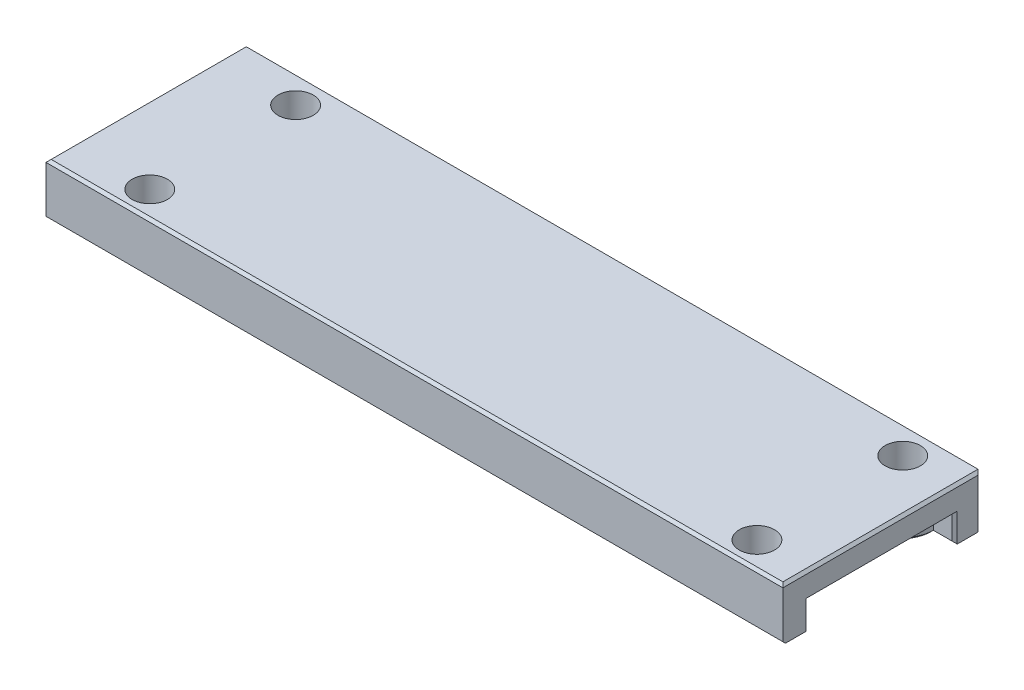
SolidWorks part; units mm, degrees
material "1060 Alloy"
ref_plane "Front Plane" through (0, 0, 0) normal (0, 0, 1) x (1, 0, 0)
ref_plane "Top Plane" through (0, 0, 0) normal (0, 1, 0) x (1, 0, 0)
ref_plane "Right Plane" through (0, 0, 0) normal (1, 0, 0) x (0, 0, -1)
sketch "Sketch1" plane through (0, 0, 0) normal (0, 1, 0) x (1, 0, 0)
  line L1 (-71, -19.05) -> (71, -19.05)
  line L2 (-71, -19.05) -> (-71, 19.05)
  line L3 (-71, 19.05) -> (71, 19.05)
  line L4 (71, -19.05) -> (71, 19.05)
  line L5 (-71, -19.05) -> (71, 19.05) construction
  line L6 (-71, 19.05) -> (71, -19.05) construction
  point P0 (0, 0)
  dimension "D1" = 142
  dimension "D2" = 38.1
extrude "Boss-Extrude1" add sketch "Sketch1" along normal mid plane 10
sketch "Sketch2" plane through (0, 0, 0) normal (1, 0, 0) x (0, 0, -1)
  line L0 (-14.05, 0) -> (14.05, 0)
  line L1 (14.05, 0) -> (14.05, -5)
  line L2 (-19.05, -5) -> (19.05, -5) construction
  line L3 (14.05, -5) -> (-14.05, -5)
  line L4 (-14.05, -5) -> (-14.05, 0)
  line L5 (-19.05, 5) -> (-19.05, -5) construction
  dimension "D1" = 5
extrude "Cut-Extrude1" cut sketch "Sketch2" against normal through all both and the other way through all
hole_wizard "Tap Drill for M8x1.25 Tap1" positions "Sketch4" profile "Sketch3" hole size "M8x1.25" standard "ANSI Metric"
sketch "Sketch4" plane through (0, 5, 0) normal (0, 1, 0) x (1, 0, 0)
  line L0 (71, 19.05) -> (-71, 19.05) construction
  line L2 (-71, 19.05) -> (-71, -19.05) construction
  line L3 (-71, -19.05) -> (71, -19.05) construction
  line L4 (71, -19.05) -> (71, 19.05) construction
  point P0 (-56, 14.05)
  point P2 (61, 14.05)
  point P4 (61, -14.05)
  point P6 (-56, -14.05)
  dimension "D1" = 5
  dimension "D2" = 15
  dimension "D3" = 15
  dimension "D4" = 5
  dimension "D5" = 10
  dimension "D6" = 10
  dimension "D7" = 5
  dimension "D8" = 5
sketch "Sketch3" plane through (-56, 5, -14.05) normal (1, 0, 0) x (0, 0, 1)
  line L0 (0, 0) -> (0, 14.0429)
  line L1 (0, 14.0429) -> (3.4, 12)
  line L2 (3.4, 12) -> (3.4, 0)
  line L5 (3.4, 0) -> (0, 0)
  line L10 (0, 14.0429) -> (-3.4, 12) construction
  line L11 (0, -6.35) -> (0, 107.95) construction
  dimension "Hole Dia." = 6.8
  dimension "Hole Depth" = 12
  dimension "Drill Angle" = 118
cosmetic thread "Cosmetic Thread1" parameters "D2"=8
cosmetic thread "Cosmetic Thread2" parameters "D2"=8
cosmetic thread "Cosmetic Thread3" parameters "D2"=8
cosmetic thread "Cosmetic Thread4" parameters "D2"=8
sketch "Sketch5" plane through (0, 0, 0) normal (0, -1, 0) x (1, 0, 0)
  line L0 (-71, 14.05) -> (-59.4, 14.05) construction
  line L1 (55.1, -14.05) -> (57.6, -14.05)
  line L2 (-52.6, 14.05) -> (-50.1, 14.05)
  line L3 (57.6, -14.05) -> (57.5688, -13.9882)
  line L4 (64.4, -14.05) -> (66.9, -14.05)
  line L5 (55.1, 14.05) -> (57.6, 14.05)
  line L6 (64.4, 14.05) -> (66.9, 14.05)
  line L7 (64.4, -14.05) -> (66.9, -14.05)
  line L8 (64.4, 14.05) -> (66.9, 14.05)
  line L9 (-61.9, 14.05) -> (-59.4, 14.05)
  line L10 (-52.6, 14.05) -> (-50.1, 14.05)
  line L11 (-61.9, -14.05) -> (-59.4, -14.05)
  line L12 (-59.4, -14.05) -> (-59.4026, -14.126)
  line L13 (-52.6, -14.05) -> (-50.1, -14.05)
  arc A0 (-59.4, 14.05) -> (-52.6, 14.05) centre (-56, 14.05) ccw
  arc A1 (-52.6, 14.05) -> (-59.4, 14.05) centre (-56, 14.05) ccw construction
  arc A2 (-61.9, 14.05) -> (-50.1, 14.05) centre (-56, 14.05) ccw
  arc A3 (-59.4, -14.05) -> (-52.6, -14.05) centre (-56, -14.05) cw
  arc A4 (-50.1, -14.05) -> (-61.9, -14.05) centre (-56, -14.05) ccw
  arc A5 (57.6, -14.05) -> (64.4, -14.05) centre (61, -14.05) cw
  arc A6 (66.9, -14.05) -> (55.1, -14.05) centre (61, -14.05) ccw
  arc A7 (57.6, 14.05) -> (64.4, 14.05) centre (61, 14.05) ccw
  arc A8 (55.1, 14.05) -> (66.9, 14.05) centre (61, 14.05) ccw
  line M1 (-71, -14.05) -> (-59.4, -14.05)
  arc M2 (-59.4, -14.05) -> (-52.6, -14.05) centre (-56, -14.05) cw
  line M3 (-52.6, -14.05) -> (57.6, -14.05)
  arc M4 (57.6, -14.05) -> (64.4, -14.05) centre (61, -14.05) cw
  line M5 (64.4, -14.05) -> (71, -14.05)
  line M7 (71, 14.05) -> (64.4, 14.05)
  arc M8 (64.4, 14.05) -> (57.6, 14.05) centre (61, 14.05) cw
  line M9 (57.6, 14.05) -> (-52.6, 14.05)
  arc M10 (-52.6, 14.05) -> (-59.4, 14.05) centre (-56, 14.05) cw
  line M11 (-59.4, 14.05) -> (-71, 14.05)
  dimension "D1" = 3.4
  dimension "D2" = 2.5
  dimension "D3" = 3.4
  dimension "D4" = 2.5
  dimension "D5" = 3.4
  dimension "D6" = 2.5
  dimension "D7" = 3.4
  dimension "D8" = 2.5
extrude "Boss-Extrude2" add sketch "Sketch5" along normal up to surface (5 mm away) contours A4 M3 M1 M2 | A2 M11 M9 M10 | A8 M9 M7 M8 | A6 M5 M3 M4 region at (61, 0, -8.2819) region at (-51.35, 0, -13.9181) region at (56.35, 0, 13.9181) region at (-51.35, 0, 13.9181) up to face at (1.25, -5, 16.15)
chamfer "Chamfer1" distance 0.5 angle 45 23 edges at (-71, -2.5, 14.05) (-71, -2.5, -14.05) (-71, 0, 0) (71, -2.5, -14.05) (71, 0, 0) (71, -2.5, 14.05) (0, -5, 19.05) (-71, 5, 0) (-71, 0, -19.05) (0, -5, -19.05) (71, 0, -19.05) (71, 5, 0) (0, 5, 19.05) (-56, -5, 8.15) (-66.45, -5, 14.05) (-66.45, -5, -14.05) (-56, -5, -8.15) (2.5, -5, -14.05) (61, -5, -8.15) (68.95, -5, -14.05) (2.5, -5, 14.05) (61, -5, 8.15) (68.95, -5, 14.05)
